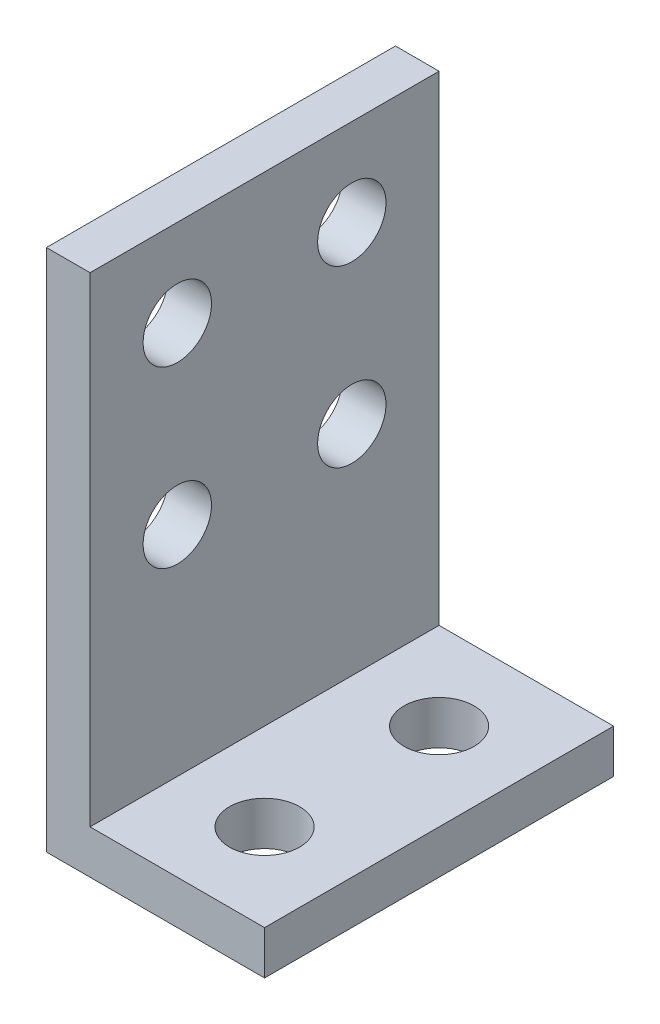
SolidWorks part; units mm, degrees
material "6061-T6 (SS)"
ref_plane "Front Plane" through (0, 0, 0) normal (0, 0, 1) x (1, 0, 0)
ref_plane "Top Plane" through (0, 0, 0) normal (0, 1, 0) x (1, 0, 0)
ref_plane "Right Plane" through (0, 0, 0) normal (1, 0, 0) x (0, 0, -1)
sketch "Sketch1" plane through (0, 0, 0) normal (0, 0, 1) x (1, 0, 0)
  line L0 (0, 0) -> (0, 38.1)
  line L1 (0, 38.1) -> (3.175, 38.1)
  line L2 (3.175, 38.1) -> (3.175, 3.175)
  line L3 (3.175, 3.175) -> (15.875, 3.175)
  line L4 (15.875, 3.175) -> (15.875, 0)
  line L5 (15.875, 0) -> (0, 0)
  dimension "D1" = 3.175
  dimension "D2" = 38.1
  dimension "D3" = 15.875
extrude "Boss-Extrude1" add sketch "Sketch1" along normal blind 25.4
sketch "Sketch2" plane through (0, 3.175, 0) normal (0, 1, 0) x (1, 0, 0)
  line L0 (15.875, -25.4) -> (3.175, -25.4) construction
  line L1 (3.175, -25.4) -> (3.175, 0) construction
  circle A0 centre (9.525, -6.35) radius 2.5527
  circle A1 centre (9.525, -19.05) radius 2.5527
  point P8 (9.968, -6.3577)
  dimension "D1" = 5.1054
  dimension "D2" = 12.7
  dimension "D3" = 6.35
  dimension "D4" = 6.35
extrude "Cut-Extrude1" cut sketch "Sketch2" against normal through all
sketch "Sketch4" plane through (0, 0, 0) normal (-1, 0, 0) x (0, 0, 1)
  line L0 (0, 38.1) -> (0, 0) construction
  line L5 (25.4, 0) -> (0, 0) construction
  circle A0 centre (6.35, 31.75) radius 2.4892
  circle A1 centre (19.05, 31.75) radius 2.4892
  circle A2 centre (19.05, 19.05) radius 2.4892
  circle A3 centre (6.35, 19.05) radius 2.4892
  point P2 (6.1863, 18.7997)
  point P13 (6.35, 6.35)
  point P14 (0, 0)
  point P15 (0, 0)
  dimension "D5" = 6.35
  dimension "D6" = 19.05
  dimension "D7" = 4.9784
  dimension "D3" = 12.7
  dimension "D4" = 12.7
  dimension "D1" = 2
  dimension "D2" = 2
extrude "Cut-Extrude2" cut sketch "Sketch4" against normal through all
